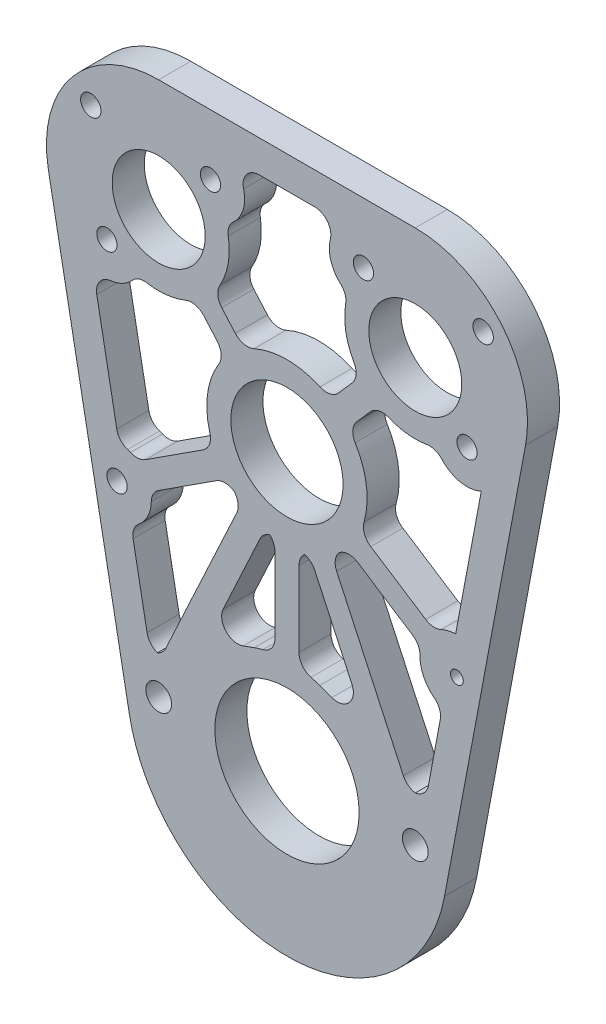
SolidWorks part; units mm, degrees
material "6061-T4 (SS)"
ref_plane "Front" through (0, 0, 0) normal (0, 0, 1) x (1, 0, 0)
ref_plane "Top" through (0, 0, 0) normal (0, 1, 0) x (1, 0, 0)
ref_plane "Right" through (0, 0, 0) normal (1, 0, 0) x (0, 0, -1)
sketch "Sketch1" plane through (0, 0, 0) normal (0, 0, 1) x (1, 0, 0)
  line L0 (35.6555, 18.6687) -> (15.1445, 39.1796) construction
  line L1 (-35.6555, 18.6687) -> (-15.1445, 39.1796) construction
  line L2 (25.4, 28.9241) -> (25.4, 10.7706) construction
  line L4 (0, -54.6862) -> (-10.7345, -77.7064) construction
  line L6 (0, -54.6862) -> (0, 0) construction
  line L7 (-25.4, -54.6862) -> (25.4, -54.6862) construction
  line L8 (0, -54.6862) -> (8.2968, -54.6862) construction
  line L9 (-25.4, 51.1491) -> (25.4, 51.1491)
  line L10 (-47.2428, 24.8204) -> (-31.2041, -60.5487)
  line L11 (47.2428, 24.8204) -> (31.2041, -60.5487)
  line L12 (-25.4, 28.9241) -> (-42.5049, 43.1147) construction
  line L13 (25.4, 28.9241) -> (42.5049, 43.1147) construction
  line L15 (-33.6423, -21.7781) -> (-28.284, -18.3095) construction
  line L16 (-33.6423, -21.7781) -> (-29.0793, -26.2415) construction
  line L17 (-27.9997, -69.6555) -> (-27.2799, -70.9303)
  circle A0 centre (0, 0) radius 33.6931 construction
  circle A1 centre (-25.4, 28.9241) radius 4.8006 construction
  circle A2 centre (25.4, 28.9241) radius 4.8006 construction
  circle A3 centre (-25.4, 28.9241) radius 14.5034 construction
  circle A4 centre (25.4, 28.9241) radius 14.5034 construction
  circle A5 centre (-15.1445, 39.1796) radius 2
  circle A6 centre (-35.6555, 18.6687) radius 2
  circle A7 centre (15.1445, 39.1796) radius 2
  circle A8 centre (35.6555, 18.6687) radius 2
  circle A9 centre (25.4, 28.9241) radius 9.2075
  circle A10 centre (-25.4, 28.9241) radius 9.2075
  circle A11 centre (0, 0) radius 11.1125
  circle A12 centre (0, 0) radius 14.0081 construction
  circle A13 centre (0, -54.6862) radius 40.6781 construction
  circle A14 centre (0, -54.6862) radius 14.2875
  circle A16 centre (25.4, -54.6862) radius 2.5527
  circle A17 centre (-25.4, -54.6862) radius 2.5527
  arc A18 (-25.4, 51.1491) -> (-47.2428, 24.8204) centre (-25.4, 28.9241) ccw
  arc A19 (47.2428, 24.8204) -> (25.4, 51.1491) centre (25.4, 28.9241) ccw
  arc A20 (-31.2041, -60.5487) -> (-27.9997, -69.6555) centre (0, -54.6862) ccw
  circle A21 centre (-38.8396, 40.0739) radius 4.7625 construction
  circle A22 centre (38.8396, 40.0739) radius 4.7625 construction
  circle A23 centre (38.8396, 40.0739) radius 1.27
  circle A24 centre (-38.8396, 40.0739) radius 1.27
  circle A25 centre (25.4, 28.9241) radius 25.4 construction
  circle A26 centre (-25.4, 28.9241) radius 25.4 construction
  arc A27 (-27.2799, -70.9303) -> (31.2041, -60.5487) centre (0, -54.6862) ccw
  circle A28 centre (-33.6423, -21.7781) radius 1.27
  circle A29 centre (-33.6423, -21.7781) radius 4.7625 construction
  circle A30 centre (33.6423, -21.7781) radius 1.27
  point P20 (25.4, 28.9241)
  point P22 (-25.4, 28.9241)
  point P31 (0, -54.6862)
  dimension "D1" = 67.3862
  dimension "D2" = 9.6012
  dimension "D3" = 29.0068
  dimension "D5" = 4
  dimension "D6" = 18.415
  dimension "D7" = 22.225
  dimension "D8" = 28.0162
  dimension "D9" = 81.3562
  dimension "D10" = 28.575
  dimension "D12" = 5.1054
  dimension "D14" = 31.75
  dimension "D15" = 22.225
  dimension "D16" = 9.525
  dimension "D17" = 2.54
  dimension "D18" = 50.8
  dimension "D21" = 2.54
  dimension "D22" = 9.525
  dimension "D4" = 45
  dimension "D11" = 50.8
extrude "Boss-Extrude1" add sketch "Sketch1" along normal blind 6.35
cosmetic thread "Hole Thread4" [suppressed] parameters "D1"=6.35, "D2"=6.35
cosmetic thread "Hole Thread5" [suppressed] parameters "D1"=6.35, "D2"=6.35
hole_wizard "#10-32 Tapped Hole1" positions "3DSketch1" profile "Sketch4" tap size "#10-32" standard "ANSI Inch"
sketch3d "3DSketch1"
  line L0 (-38.8396, 40.0739, 6.35) -> (-38.8396, 40.0739, 0) construction
  line L1 (38.8396, 40.0739, 6.35) -> (38.8396, 40.0739, 0) construction
  line L2 (-33.6423, -21.7781, 6.35) -> (-33.6423, -21.7781, 0) construction
  point P0 (-38.8396, 40.0739, 6.35)
  point P4 (38.8396, 40.0739, 6.35)
  point P8 (-33.6423, -21.7781, 6.35)
sketch "Sketch4" plane through (-38.8396, 40.0739, 6.35) normal (1, 0, 0) x (0, -1, 0)
  line L0 (0, 0) -> (0, 13.2428)
  line L1 (0, 13.2428) -> (2.0193, 12.0294)
  line L2 (2.0193, 12.0294) -> (2.0193, 0)
  line L5 (2.0193, 0) -> (0, 0)
  line L10 (0, 13.2428) -> (-2.0193, 12.0294) construction
  line L11 (0, -6.35) -> (0, 107.95) construction
  dimension "Tap Drill Dia." = 4.0386
  dimension "Tap Drill Depth" = 12.0294
  dimension "Drill Angle" = 118
cosmetic thread "Hole Thread1" parameters "D1"=6.35, "D2"=4.826
cosmetic thread "Hole Thread2" parameters "D1"=6.35, "D2"=4.826
cosmetic thread "Hole Thread3" parameters "D1"=6.35, "D2"=4.826
sketch "Sketch5" plane through (0, 0, 6.35) normal (0, 0, 1) x (1, 0, 0)
  line L0 (0, 0) -> (-25.4, -54.6862) construction
  line L1 (-2.3036, 1.07) -> (-27.7036, -53.6162)
  line L2 (2.3036, -1.07) -> (-23.0964, -55.7562)
  line L3 (6.4817, -36.7728) -> (16.0648, -40.2403)
  line L4 (24.9633, -59.3762) -> (41.002, 25.9929)
  line L5 (-22.4322, -66.6007) -> (-21.7884, -67.7408)
  line L6 (-22.4322, -66.6007) -> (-21.7884, -67.7408)
  line L7 (24.9633, -59.3762) -> (41.002, 25.9929)
  line L8 (-6.4817, -36.7728) -> (-16.0648, -40.2403)
  line L13 (25.4, 44.7991) -> (-25.4, 44.7991)
  line L14 (-41.002, 25.9929) -> (-24.9633, -59.3762)
  line L18 (25.4, 44.7991) -> (-25.4, 44.7991)
  line L19 (-41.002, 25.9929) -> (-24.9633, -59.3762)
  line L20 (25.4, 28.9241) -> (0, 0) construction
  line L21 (0, 0) -> (-25.4, 28.9241) construction
  line L22 (-33.6423, -21.7781) -> (0, 0) construction
  line L23 (25.4, -54.6862) -> (0, 0) construction
  line L24 (0, 0) -> (33.6423, -21.7781) construction
  line L25 (0, -54.6862) -> (0, 0) construction
  line L26 (23.6107, 30.4954) -> (0, 3.6088)
  line L27 (0, 3.6088) -> (-23.6107, 30.4954)
  line L28 (27.1893, 27.3529) -> (0, -3.6088)
  line L29 (0, -3.6088) -> (-27.1893, 27.3529)
  line L30 (-34.9363, -19.7792) -> (-1.294, 1.999)
  line L31 (-2.3813, -54.6862) -> (-2.3813, 0)
  line L32 (23.2403, -55.6893) -> (-2.1597, -1.0031)
  line L33 (1.294, 1.999) -> (34.9363, -19.7792)
  line L34 (-32.3483, -23.7771) -> (1.294, -1.999)
  line L35 (2.3813, -54.6862) -> (2.3813, 0)
  line L36 (27.5597, -53.6831) -> (2.1597, 1.0031)
  line L37 (-1.294, -1.999) -> (32.3483, -23.7771)
  circle A0 centre (33.6423, -21.7781) radius 1.27 construction
  circle A9 centre (-25.4, 28.9241) radius 13.97
  circle A10 centre (-25.4, 28.9241) radius 13.97
  circle A12 centre (-15.1445, 39.1796) radius 6.7625
  circle A13 centre (-15.1445, 39.1796) radius 6.7625
  arc A14 (-21.7884, -67.7408) -> (24.9633, -59.3762) centre (0, -54.6862) ccw
  arc A15 (41.002, 25.9929) -> (25.4, 44.7991) centre (25.4, 28.9241) ccw
  arc A16 (-25.4, 44.7991) -> (-41.002, 25.9929) centre (-25.4, 28.9241) ccw
  arc A17 (-24.9633, -59.3762) -> (-22.4322, -66.6007) centre (0, -54.6862) ccw
  arc A18 (-21.7884, -67.7408) -> (24.9633, -59.3762) centre (0, -54.6862) ccw
  arc A19 (41.002, 25.9929) -> (25.4, 44.7991) centre (25.4, 28.9241) ccw
  arc A20 (-25.4, 44.7991) -> (-41.002, 25.9929) centre (-25.4, 28.9241) ccw
  arc A21 (-24.9633, -59.3762) -> (-22.4322, -66.6007) centre (0, -54.6862) ccw
  circle A30 centre (-35.6555, 18.6687) radius 6.7625
  circle A31 centre (-35.6555, 18.6687) radius 6.7625
  circle A33 centre (25.4, 28.9241) radius 13.97
  circle A34 centre (25.4, 28.9241) radius 13.97
  circle A36 centre (15.1445, 39.1796) radius 6.7625
  circle A37 centre (15.1445, 39.1796) radius 6.7625
  circle A39 centre (35.6555, 18.6687) radius 6.7625
  circle A40 centre (35.6555, 18.6687) radius 6.7625
  circle A43 centre (33.6423, -21.7781) radius 7.3152
  circle A45 centre (0, 0) radius 15.875
  circle A46 centre (0, 0) radius 15.875
  circle A48 centre (-33.6423, -21.7781) radius 6.7818
  circle A49 centre (-33.6423, -21.7781) radius 6.7818
  circle A51 centre (0, -54.6862) radius 19.05
  circle A52 centre (0, -54.6862) radius 19.05
  circle A54 centre (25.4, -54.6862) radius 8.9027
  circle A55 centre (25.4, -54.6862) radius 8.9027
  circle A57 centre (-25.4, -54.6862) radius 7.3152
  circle A58 centre (-25.4, -54.6862) radius 7.3152
  circle A60 centre (-38.8396, 40.0739) radius 6.7818
  circle A61 centre (-38.8396, 40.0739) radius 6.7818
  circle A63 centre (38.8396, 40.0739) radius 6.7818
  circle A64 centre (38.8396, 40.0739) radius 6.7818
  dimension "D8" = 2.54
  dimension "D1" = 6.35
  dimension "D2" = 4.7625
  dimension "D3" = 4.7625
  dimension "D4" = 4.7625
  dimension "D5" = 4.7625
  dimension "D6" = 4.7625
  dimension "D7" = 4.7625
  dimension "D9" = 4.7625
  dimension "D10" = 4.7625
  dimension "D11" = 4.7625
  dimension "D12" = 6.35
  dimension "D13" = 4.7625
  dimension "D14" = 4.7625
  dimension "D15" = 4.7625
  dimension "D16" = 2.3813
  dimension "D17" = 2.3813
  dimension "D18" = 2.3813
  dimension "D19" = 2.3813
  dimension "D20" = 2.54
extrude "Cut-Extrude2" cut sketch "Sketch5" against normal through all
fillet "Fillet2" radius 3.175 40 edges at (23.9461, -45.903, 3.175) (8.7713, -13.2318, 3.175) (11.8816, -10.5282, 3.175) (26.5419, -20.0184, 3.175) (-27.1775, -47.5903, 3.175) (-30.8646, -27.965, 3.175) (-33.2995, -15.005, 3.175) (-27.0177, -20.3264, 3.175) (-11.8816, -10.5282, 3.175) (-2.3813, -15.6954, 3.175) (-2.3813, -35.7856, 3.175) (-38.4708, 12.5201, 3.175) (-18.1061, 17.0094, 3.175) (-12.1458, 10.2222, 3.175) (-14.4697, -6.5302, 3.175) (-29.6057, -16.3285, 3.175) (12.1458, 10.2222, 3.175) (18.1061, 17.0094, 3.175) (29.625, 15.6083, 3.175) (29.1299, -16.0205, 3.175) (14.4697, -6.5302, 3.175) (2.3813, -35.7856, 3.175) (2.3813, -15.6954, 3.175) (4.452, -15.238, 3.175) (-29.625, 15.6083, 3.175) (-8.5673, 13.3648, 3.175) (-14.5276, 20.152, 3.175) (-12.0842, 33.1492, 3.175) (11.3826, 44.7991, 3.175) (12.0842, 33.1492, 3.175) (14.5276, 20.152, 3.175) (8.5673, 13.3648, 3.175) (-11.3826, 44.7991, 3.175) (30.7636, -28.5031, 3.175) (27.4711, -46.0278, 3.175) (-8.9048, -13.1423, 3.175) (-24.8139, -47.3945, 3.175) (-4.2975, -15.2822, 3.175) (16.0648, -40.2403, 3.175) (-15.8544, -40.1642, 3.175)
sketch "Sketch6" [suppressed] plane through (0, 0, 6.35) normal (0, 0, 1) x (1, 0, 0)
  circle A0 centre (-38.8396, 40.0739) radius 2.5527
  circle A1 centre (38.8396, 40.0739) radius 2.5527
  circle A2 centre (-33.6423, -21.7781) radius 2.5527
  dimension "D1" = 5.1054
extrude "Cut-Extrude3" [suppressed] cut sketch "Sketch6" against normal through all
sketch "Sketch7" [suppressed] plane through (0, 0, 6.35) normal (0, 0, 1) x (1, 0, 0)
  circle A0 centre (-35.6555, 18.6687) radius 2.5
  circle A1 centre (-15.1445, 39.1796) radius 2.5
  circle A2 centre (15.1445, 39.1796) radius 2.5
  circle A3 centre (35.6555, 18.6687) radius 2.5
  dimension "D1" = 5
extrude "Cut-Extrude4" [suppressed] cut sketch "Sketch7" against normal through all
hole_wizard "1/4-20 Tapped Hole1" [suppressed] positions "3DSketch2" profile "Sketch8" tap size "1/4-20" standard "ANSI Inch"
sketch3d "3DSketch2"
  line L0 (-25.4, -54.6862, 6.35) -> (-25.4, -54.6862, 0) construction
  line L1 (25.4, -54.6862, 6.35) -> (25.4, -54.6862, 0) construction
  point P0 (-25.4, -54.6862, 6.35)
  point P4 (25.4, -54.6862, 6.35)
sketch "Sketch8" plane through (-25.4, -54.6862, 6.35) normal (1, 0, 0) x (0, -1, 0)
  line L0 (0, 0) -> (0, 18.0438)
  line L1 (0, 18.0438) -> (2.5527, 16.51)
  line L2 (2.5527, 16.51) -> (2.5527, 0)
  line L5 (2.5527, 0) -> (0, 0)
  line L10 (0, 18.0438) -> (-2.5527, 16.51) construction
  line L11 (0, -6.35) -> (0, 107.95) construction
  dimension "Tap Drill Dia." = 5.1054
  dimension "Tap Drill Depth" = 16.51
  dimension "Drill Angle" = 118
move or copy body "Body-Move/Copy3" [suppressed] bodies to move or copy 106
move or copy body "Body-Move/Copy2" [suppressed] bodies to move or copy 111
move or copy body "Body-Move/Copy1" [suppressed] bodies to move or copy 110
